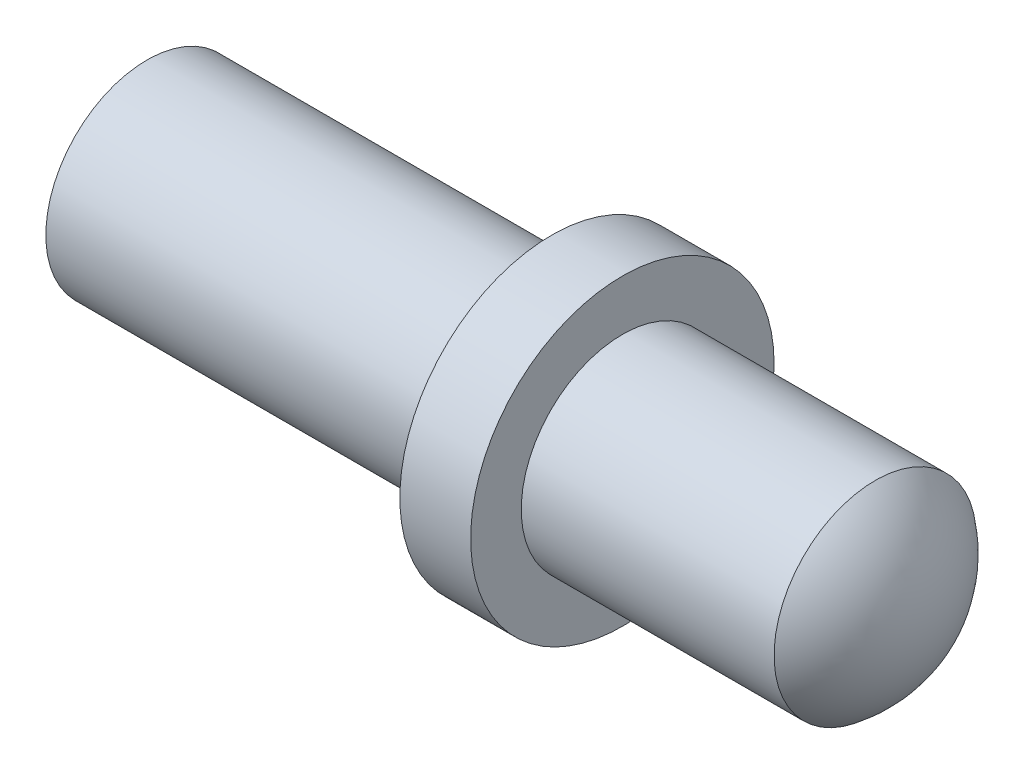
SolidWorks part; units mm, degrees
material "Alliage 7079"
ref_plane "Face" through (0, 0, 0) normal (0, 0, 1) x (1, 0, 0)
ref_plane "Dessus" through (0, 0, 0) normal (0, 1, 0) x (1, 0, 0)
ref_plane "Droite" through (0, 0, 0) normal (1, 0, 0) x (0, 0, -1)
sketch "Esquisse1" plane through (0, 0, 0) normal (0, 0, 1) x (1, 0, 0)
  line L0 (0, 0) -> (0, 2)
  line L1 (0, 2) -> (8, 2)
  line L2 (8, 2) -> (8, 3)
  line L3 (8, 3) -> (9.4, 3)
  line L4 (9.4, 3) -> (9.4, 2)
  line L5 (9.4, 2) -> (14.4, 2)
  line L6 (14.4, 2) -> (14.4, 0)
  line L7 (14.4, 0) -> (0, 0)
  dimension "D1" = 2
  dimension "D2" = 2
  dimension "D3" = 3
  dimension "D4" = 8
  dimension "D5" = 1.4
  dimension "D6" = 5
revolve "Révolution1" add sketch "Esquisse1" angle 360 about L7
dome "Dôme1" faces to dome 1 distance 1 reverse direction no elliptical dome no face at (14.4, 0, -2) parameters "D1"=1
